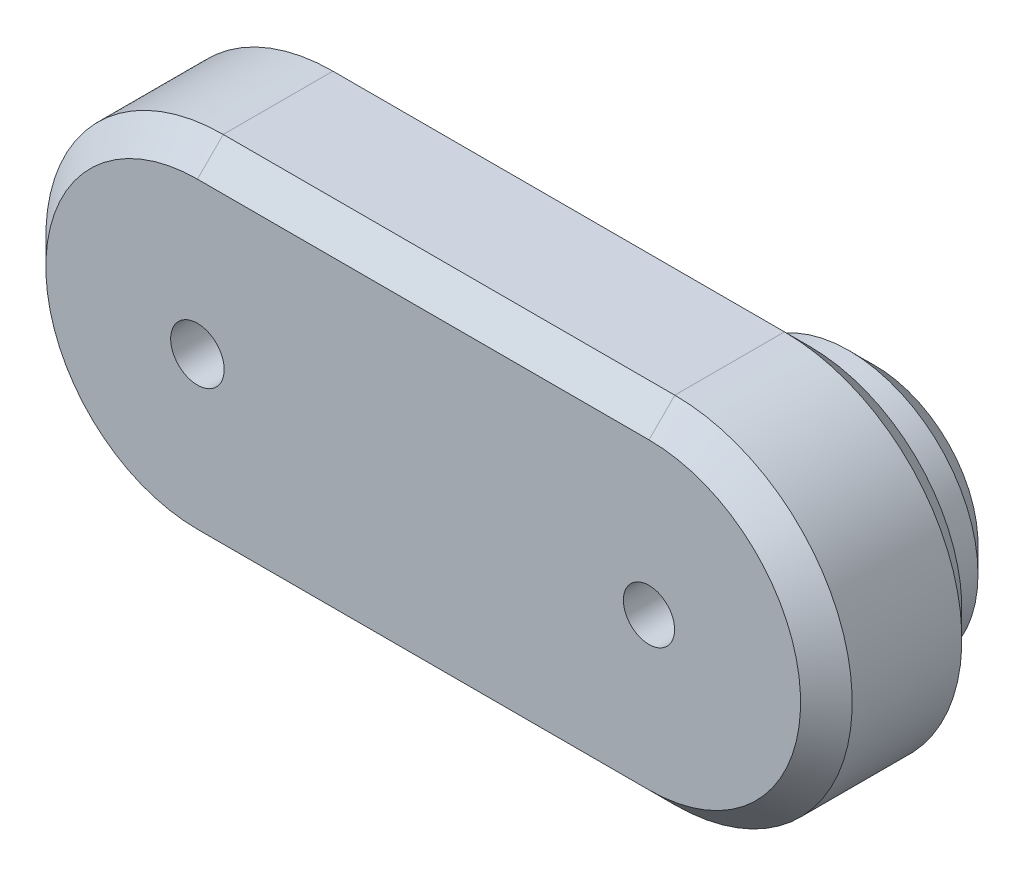
SolidWorks part; units mm, degrees
ref_plane "Front Plane" through (0, 0, 0) normal (0, 0, 1) x (1, 0, 0)
ref_plane "Top Plane" through (0, 0, 0) normal (0, 1, 0) x (1, 0, 0)
ref_plane "Right Plane" through (0, 0, 0) normal (1, 0, 0) x (0, 0, -1)
sketch "Sketch2" plane through (0, 0, 0) normal (0, 0, 1) x (1, 0, 0)
  line L0 (70, 27.5) -> (0, 27.5)
  line L3 (70, 0) -> (0, 0) construction
  line L6 (70, -27.5) -> (0, -27.5)
  circle A0 centre (0, 0) radius 18 construction
  circle A1 centre (0, 0) radius 4.15
  circle A5 centre (-18, 0) radius 2.25 construction
  arc A10 (0, 27.5) -> (0, -27.5) centre (0, 0) ccw
  circle A11 centre (70, 0) radius 38.1 construction
  circle A12 centre (-16.2174, 7.8099) radius 2.25 construction
  circle A13 centre (-11.2228, 14.073) radius 2.25 construction
  circle A14 centre (-4.0054, 17.5487) radius 2.25 construction
  circle A15 centre (4.0054, 17.5487) radius 2.25 construction
  circle A16 centre (11.2228, 14.073) radius 2.25 construction
  circle A17 centre (16.2174, 7.8099) radius 2.25 construction
  circle A18 centre (18, 0) radius 2.25 construction
  circle A19 centre (16.2174, -7.8099) radius 2.25 construction
  circle A20 centre (11.2228, -14.073) radius 2.25 construction
  circle A21 centre (4.0054, -17.5487) radius 2.25 construction
  circle A22 centre (-4.0054, -17.5487) radius 2.25 construction
  circle A23 centre (-11.2228, -14.073) radius 2.25 construction
  circle A24 centre (-16.2174, -7.8099) radius 2.25 construction
  circle A25 centre (70, 0) radius 3.9687
  arc A26 (70, -27.5) -> (70, 27.5) centre (70, 0) ccw
  point P6 (0, 0)
  point P41 (29.2536, 24.3509)
  dimension "D1" = 36
  dimension "D2" = 8.3
  dimension "D3" = 4.5
  dimension "D4" = 14
  dimension "D5" = 76.2
  dimension "D6" = 70
  dimension "D9" = 55
  dimension "D10" = 7.9375
extrude "Boss-Extrude1" add sketch "Sketch2" along normal blind 25
sketch "Sketch3" plane through (0, 0, 0) normal (0, 0, -1) x (-1, 0, 0)
  circle A0 centre (0, 0) radius 18 construction
  circle A1 centre (-18, 0) radius 2.25
  circle A2 centre (-16.2174, 7.8099) radius 2.25
  circle A3 centre (-11.2228, 14.073) radius 2.25
  circle A4 centre (-4.0054, 17.5487) radius 2.25
  circle A5 centre (4.0054, 17.5487) radius 2.25
  circle A6 centre (11.2228, 14.073) radius 2.25
  circle A7 centre (16.2174, 7.8099) radius 2.25
  circle A8 centre (18, 0) radius 2.25
  circle A9 centre (16.2174, -7.8099) radius 2.25
  circle A10 centre (11.2228, -14.073) radius 2.25
  circle A11 centre (4.0054, -17.5487) radius 2.25
  circle A12 centre (-4.0054, -17.5487) radius 2.25
  circle A13 centre (-11.2228, -14.073) radius 2.25
  circle A14 centre (-16.2174, -7.8099) radius 2.25
  point P5 (0, 0)
  point P34 (0, 0)
  dimension "D1" = 4.5
  dimension "D3" = 36
  dimension "D2" = 14
extrude "Boss-Extrude2" add sketch "Sketch3" along normal blind 2.25
chamfer "Chamfer1" distance 1.5 angle 45 14 edges at (13.9674, -7.8099, -2.25) (8.9728, -14.073, -2.25) (1.7554, -17.5487, -2.25) (-6.2554, -17.5487, -2.25) (-18.4674, -7.8099, -2.25) (-20.25, 0, -2.25) (-18.4674, 7.8099, -2.25) (-13.4728, 14.073, -2.25) (-6.2554, 17.5487, -2.25) (1.7554, 17.5487, -2.25) (8.9728, 14.073, -2.25) (13.9674, 7.8099, -2.25) (15.75, 0, -2.25) (-13.4728, -14.073, -2.25)
sketch "Sketch4" plane through (0, 0, 25) normal (0, 0, 1) x (1, 0, 0)
  circle A0 centre (0, 0) radius 4.15
  circle A1 centre (0, 0) radius 22.5
  dimension "D1" = 45
sketch "Sketch5" plane through (0, 0, 0) normal (0, 0, -1) x (-1, 0, 0)
  circle A0 centre (-70, 0) radius 3.9687
  circle A1 centre (-70, 0) radius 20
  circle A2 centre (-70, 0) radius 3.9687 construction
  dimension "D1" = 40
extrude "Boss-Extrude4" add sketch "Sketch5" along normal blind 10
chamfer "Chamfer2" distance 4 angle 45 1 edges at (50, 0, -10)
chamfer "Chamfer3" distance 4 angle 45 8 edges at (-27.5, 0, 25) (35, -27.5, 25) (35, 27.5, 25) (97.5, 0, 25) (-27.5, 0, 0) (35, -27.5, 0) (35, 27.5, 0) (97.5, 0, 0)
